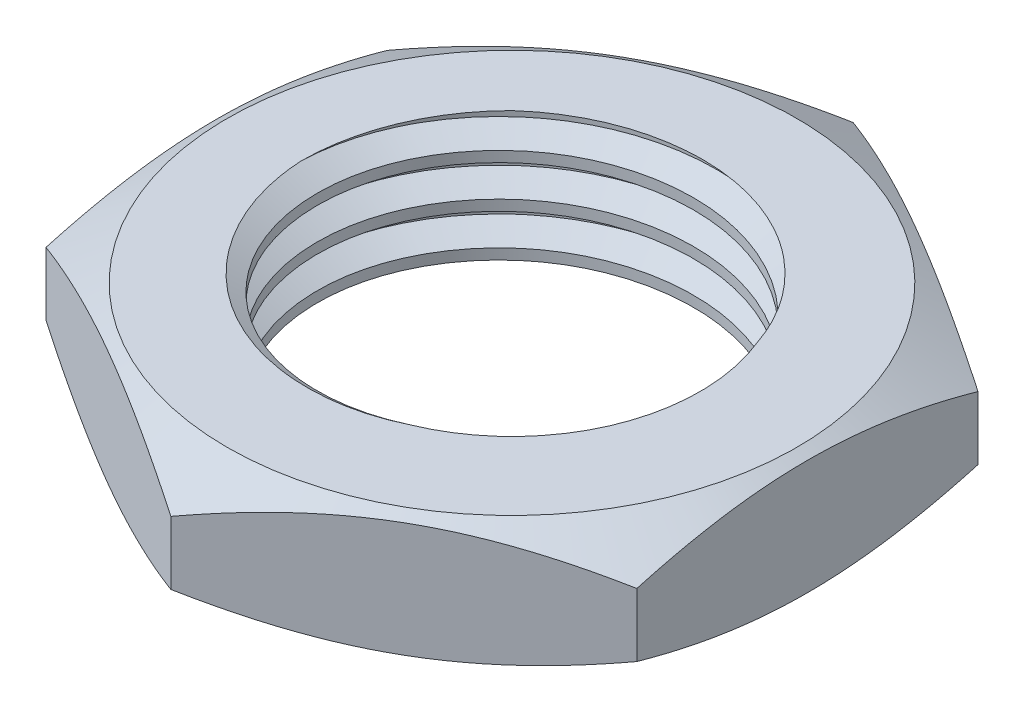
SolidWorks part; units mm, degrees
ref_plane "Front Plane" through (0, 0, 0) normal (0, 0, 1) x (1, 0, 0)
ref_plane "Top Plane" through (0, 0, 0) normal (0, 1, 0) x (1, 0, 0)
ref_plane "Right Plane" through (0, 0, 0) normal (1, 0, 0) x (0, 0, -1)
sketch "Sketch1" plane through (0, 0, 0) normal (0, 1, 0) x (1, 0, 0)
  line L1 (0, 8.0829) -> (-7, 4.0415)
  line L2 (-7, 4.0415) -> (-7, -4.0415)
  line L3 (-7, -4.0415) -> (0, -8.0829)
  line L4 (0, -8.0829) -> (7, -4.0415)
  line L5 (7, -4.0415) -> (7, 4.0415)
  line L6 (7, 4.0415) -> (0, 8.0829)
  circle A0 centre (0, 0) radius 5
  circle A1 centre (0, 0) radius 7 construction
  dimension "D1" = 10
  dimension "D2" = 14
extrude "Boss-Extrude1" add sketch "Sketch1" along normal blind 3
sketch "Sketch2" plane through (0, 0, 0) normal (1, 0, 0) x (0, 0, -1)
  line L0 (-8.0829, 3) -> (-6.75, 3)
  line L1 (-8.0829, 3) -> (-4.0415, 3) construction
  line L2 (-6.75, 3) -> (-8.0829, 2.25)
  line L3 (-8.0829, 3) -> (-8.0829, 0) construction
  line L4 (-8.0829, 2.25) -> (-8.0829, 3)
  line L5 (-8.0829, 0) -> (-8.0829, 0.75)
  line L6 (-8.0829, 0.75) -> (-6.75, 0)
  line L7 (-8.0829, 0) -> (-4.0415, 0) construction
  line L8 (-6.75, 0) -> (-8.0829, 0)
  line L9 (0, 0) -> (0, -1.1798) construction
  dimension "D1" = 1.5
  dimension "D2" = 13.5
revolve "Cut-Revolve1" cut sketch "Sketch2" angle 360 about L9
thread "Thread1" pitch 1 method extrude trim with start face yes trim with end face yes profile "Thread Profile1" start angle 0, offset 1, length 0, pitch 1, diameter 10
ref_plane "Plane1" through (-5, 4, 0) normal (0, 0, 1) x (-1, 0, 0)
sketch "Thread Profile1" plane through (-5, 4, 0) normal (0, 0, 1) x (-1, 0, 0)
  line L0 (0, 0) -> (0, 1) construction
  line L11 (0, 0) -> (0, 0.875)
  line L12 (0, 0.875) -> (-0.5413, 0.5625)
  line L13 (-0.5413, 0.5625) -> (-0.5413, 0.3125)
  line L15 (-0.5413, 0.3125) -> (0, 0)
  line L17 (-0.5413, 0.4375) -> (0, 0.4375) construction
  point P2 (0, 0)
  dimension "Pitch" = 1
  dimension "Profile_Angle" = 60
  dimension "Profile_Land" = 0.25
  dimension "Profile_Height" = 0.5413
